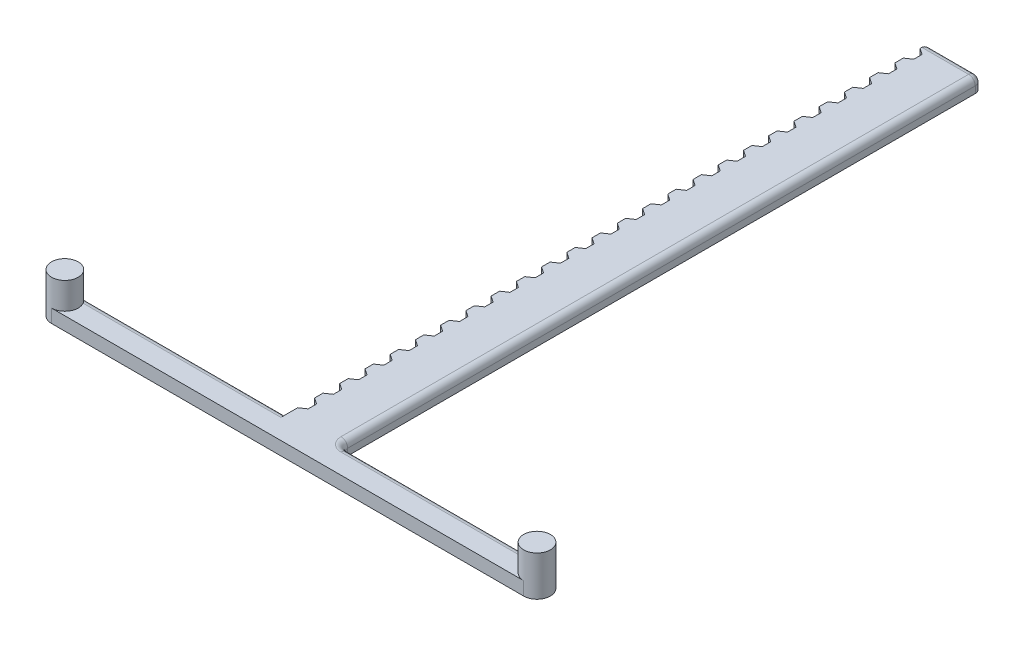
SolidWorks part; units mm, degrees
ref_plane "Front Plane" through (0, 0, 0) normal (0, 0, 1) x (1, 0, 0)
ref_plane "Top Plane" through (0, 0, 0) normal (0, 1, 0) x (1, 0, 0)
ref_plane "Right Plane" through (0, 0, 0) normal (1, 0, 0) x (0, 0, -1)
sketch "Sketch1" plane through (0, 0, 0) normal (0, 1, 0) x (1, 0, 0)
  line L0 (-6.35, 0) -> (-56.134, 0)
  line L1 (-6.35, 152.4) -> (6.35, 152.4)
  line L2 (-6.35, 152.4) -> (-6.35, 0)
  line L4 (6.35, 152.4) -> (6.35, 0)
  line L5 (56.134, 0) -> (6.35, 0)
  line L7 (56.134, -6.35) -> (-56.134, -6.35)
  arc A0 (-56.134, 0) -> (-56.134, -6.35) centre (-56.134, -3.175) ccw
  arc A1 (56.134, -6.35) -> (56.134, 0) centre (56.134, -3.175) ccw
  dimension "D4" = 6.35
  dimension "D5" = 6.35
  dimension "D2" = 12.7
  dimension "D3" = 6.35
extrude "Boss-Extrude1" add sketch "Sketch1" along normal blind 3.175
sketch "Sketch2" plane through (0, 3.175, 0) normal (0, 1, 0) x (1, 0, 0)
  line L0 (-6.35, 150.4) -> (-4.8695, 149.4)
  line L1 (-6.35, 152.4) -> (-6.35, 0) construction
  line L2 (-4.8695, 149.4) -> (-4.8695, 147.4)
  line L3 (-4.8695, 147.4) -> (-6.35, 146.4)
  line L4 (-6.35, 146.4) -> (-6.35, 150.4)
  line L5 (-6.35, 150.4) -> (6.35, 150.4) construction
  line L6 (6.35, 0) -> (6.35, 152.4) construction
  line L7 (-6.35, 146.4) -> (6.35, 146.4) construction
  line L8 (-4.8695, 149.4) -> (6.35, 149.4) construction
  line L9 (-4.8695, 147.4) -> (6.35, 147.4) construction
  line L10 (6.35, 152.4) -> (-6.35, 152.4) construction
  dimension "D1" = 2
  dimension "D2" = 1
  dimension "D3" = 1
  dimension "D4" = 2
extrude "Cut-Extrude1" cut sketch "Sketch2" against normal blind 3.175
pattern_linear "LPattern1" count 25 spacing 6 along (0, 0, 1) of "Cut-Extrude1"
sketch "Sketch3" plane through (0, 3.175, 0) normal (0, 1, 0) x (1, 0, 0)
  circle A0 centre (-56.134, -3.175) radius 3.175
  circle A1 centre (56.134, -3.175) radius 3.175
extrude "Boss-Extrude2" add sketch "Sketch3" along normal blind 6.35
fillet "Fillet1" radius 1.5875 7 edges at (0, 3.175, -152.4) (-6.35, 1.5875, -152.4) (6.35, 1.5875, -152.4) (6.35, 1.5875, 0) (6.35, 3.175, -76.2) (31.242, 3.175, 0) (-31.242, 3.175, 0)
